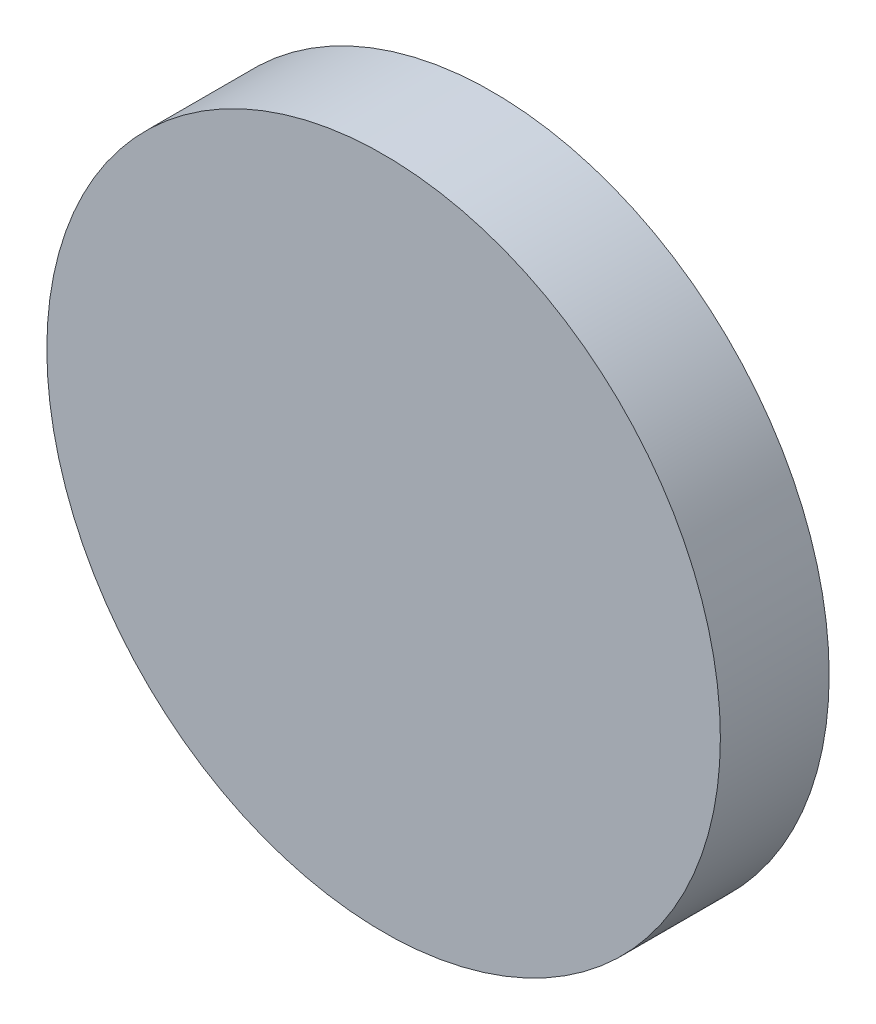
SolidWorks part; units mm, degrees
ref_plane "Front Plane" through (0, 0, 0) normal (0, 0, 1) x (1, 0, 0)
ref_plane "Top Plane" through (0, 0, 0) normal (0, 1, 0) x (1, 0, 0)
ref_plane "Right Plane" through (0, 0, 0) normal (1, 0, 0) x (0, 0, -1)
sketch "Sketch1" plane through (0, 0, 0) normal (0, 0, 1) x (1, 0, 0)
  circle A0 centre (0, 0) radius 30.955
  dimension "D1" = 61.91
extrude "Boss-Extrude1" add sketch "Sketch1" along normal blind 10
